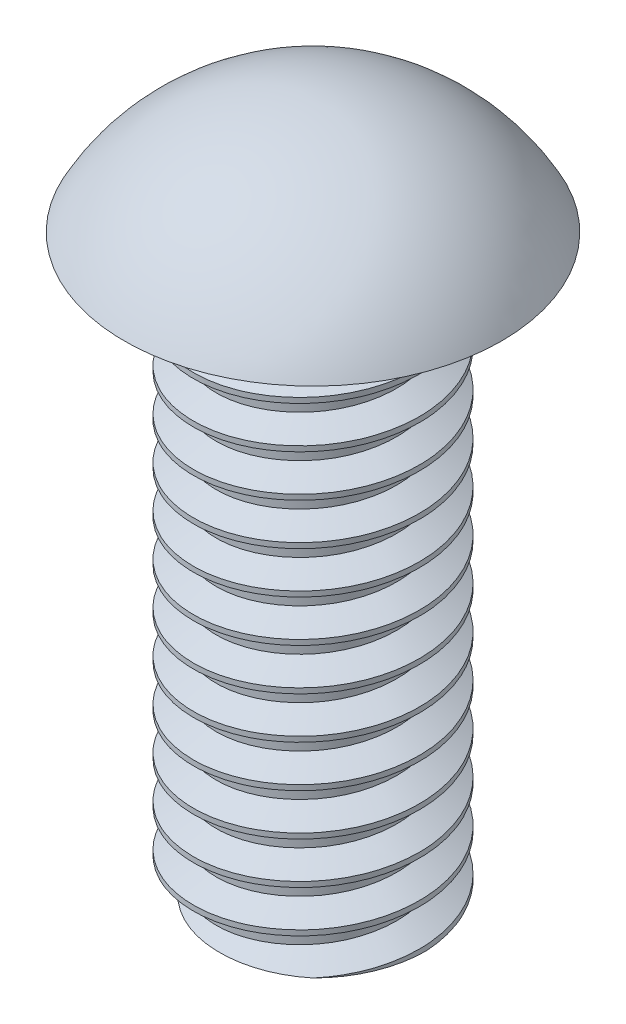
SolidWorks part; units mm, degrees
material "PET"
ref_plane "Front Plane" through (0, 0, 0) normal (0, 0, 1) x (1, 0, 0)
ref_plane "Top Plane" through (0, 0, 0) normal (0, 1, 0) x (1, 0, 0)
ref_plane "Right Plane" through (0, 0, 0) normal (1, 0, 0) x (0, 0, -1)
sketch "Sketch1" plane through (0, 0, 0) normal (0, 0, 1) x (1, 0, 0)
  line L0 (9.7824, 12.1851) -> (12.3224, 12.1851)
  line L2 (5.9724, 12.1851) -> (5.9724, -6.8649)
  line L3 (5.9724, -6.8649) -> (9.7824, -6.8649)
  line L4 (9.7824, 12.1851) -> (9.7824, -6.8649)
  line L5 (5.9724, 12.1851) -> (5.9724, 15.9951)
  arc A0 (5.9724, 15.9951) -> (12.3224, 12.1851) centre (5.9724, 8.7985) cw
  dimension "D1" = 19.05
  dimension "D2" = 3.81
  dimension "D3" = 2.54
  dimension "D4" = 3.81
revolve "Revolve1" add sketch "Sketch1" angle 360 about L2
thread "Thread1" pitch 1.4111 method cut profile "Thread Profile1" start angle 0, offset 0, length 0, pitch 1.4111, diameter 7.62
ref_plane "Plane1" through (2.1624, 12.1851, 0) normal (0, 0, 1) x (-1, 0, 0)
sketch "Thread Profile1" plane through (2.1624, 12.1851, 0) normal (0, 0, 1) x (-1, 0, 0)
  line L0 (0, 0) -> (0, 1.4111) construction
  line L11 (0, 0) -> (0, 1.2347)
  line L12 (0, 1.2347) -> (-0.7638, 0.7937)
  line L13 (-0.7638, 0.7937) -> (-0.7638, 0.441)
  line L15 (-0.7638, 0.441) -> (0, 0)
  line L17 (-0.7638, 0.6174) -> (0, 0.6174) construction
  point P2 (0, 0)
  dimension "Pitch" = 1.4111
  dimension "Profile_Angle" = 60
  dimension "Profile_Land" = 0.3528
  dimension "Profile_Height" = 0.7638
